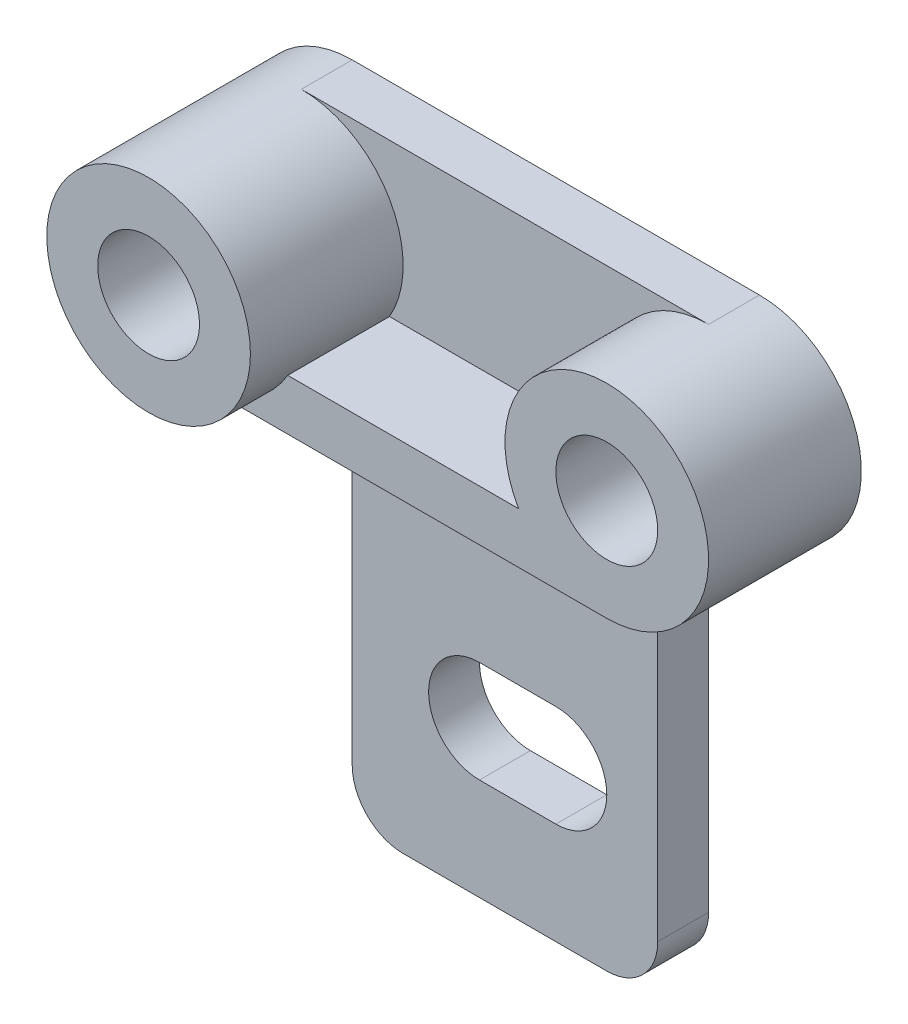
SolidWorks part; units mm, degrees
ref_plane "Front Plane" through (0, 0, 0) normal (0, 0, 1) x (1, 0, 0)
ref_plane "Top Plane" through (0, 0, 0) normal (0, 1, 0) x (1, 0, 0)
ref_plane "Right Plane" through (0, 0, 0) normal (1, 0, 0) x (0, 0, -1)
sketch "Sketch1" plane through (0, 0, 0) normal (0, 0, 1) x (1, 0, 0)
  line L0 (-5, 30) -> (10, 30) construction
  line L1 (-30, 0) -> (30, 0)
  line L2 (-30, 0) -> (-30, 80)
  line L3 (-30, 80) -> (30, 80)
  line L4 (30, 0) -> (30, 80)
  line L5 (-5, 40) -> (10, 40)
  line L6 (-5, 20) -> (10, 20)
  line L7 (-40, 80) -> (40, 80)
  line L8 (-40, 120) -> (40, 120)
  line L9 (22.6795, 90) -> (-22.6795, 90)
  arc A0 (-5, 40) -> (-5, 20) centre (-5, 30) ccw
  arc A1 (10, 20) -> (10, 40) centre (10, 30) ccw
  circle A2 centre (-40, 100) radius 10
  circle A3 centre (40, 100) radius 10
  circle A4 centre (-40, 100) radius 20
  circle A5 centre (40, 100) radius 20
  point P7 (2.5, 30)
  point P24 (0, 120)
  point P25 (0, 0)
  point P26 (-66.0441, 37.1556)
  point P28 (0, 0)
  point P29 (0, 80)
  dimension "D1" = 20
  dimension "D2" = 40
  dimension "D6" = 10
  dimension "D3" = 80
  dimension "D4" = 60
  dimension "D5" = 15
  dimension "D7" = 100
  dimension "D8" = 20
  dimension "D9" = 30
  dimension "D10" = 10
extrude "Boss-Extrude1" add sketch "Sketch1" along normal blind 10 contours L2 L1 L4 L3 | L6 A1 L5 A0
extrude "Boss-Extrude2" add sketch "Sketch1<3>" along normal blind 10 separate body contours A5 L8 A4 L9 region at (0, 106.1452, 0)
sketch "Sketch1<3>" plane through (0, 0, 0) normal (0, 0, 1) x (1, 0, 0) same geometry as "Sketch1"
extrude "Boss-Extrude3" add sketch "Sketch1<4>" along normal blind 30 contours A5 A3 | A5 L9 A4 L7 L3 region at (0, 84.6013, 0) region at (30.2828, 83.1694, 0)
sketch "Sketch1<4>" plane through (0, 0, 0) normal (0, 0, 1) x (1, 0, 0) same geometry as "Sketch1"
extrude "Boss-Extrude4" add sketch "Sketch1<5>" along normal blind 40 contours A4 A2 region at (-59.4343, 100, 0)
sketch "Sketch1<5>" plane through (0, 0, 0) normal (0, 0, 1) x (1, 0, 0) same geometry as "Sketch1"
fillet "Fillet1" radius 10 2 edges at (-30, 0, 5) (30, 0, 5)
